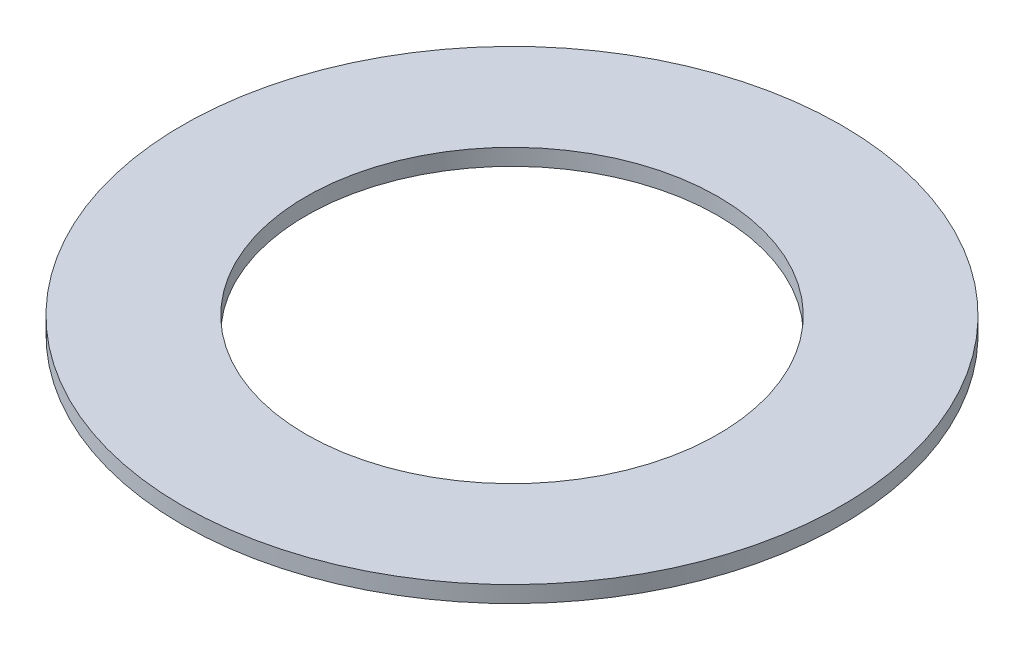
SolidWorks part; units mm, degrees
ref_plane "Front Plane" through (0, 0, 0) normal (0, 0, 1) x (1, 0, 0)
ref_plane "Top Plane" through (0, 0, 0) normal (0, 1, 0) x (1, 0, 0)
ref_plane "Right Plane" through (0, 0, 0) normal (1, 0, 0) x (0, 0, -1)
sketch "Sketch2" plane through (0, 0, 0) normal (0, 1, 0) x (1, 0, 0)
  circle A0 centre (0, 0) radius 20
  circle A1 centre (0, 0) radius 12.5
  dimension "D1" = 25
  dimension "D2" = 40
extrude "Boss-Extrude1" add sketch "Sketch2" along normal blind 1
